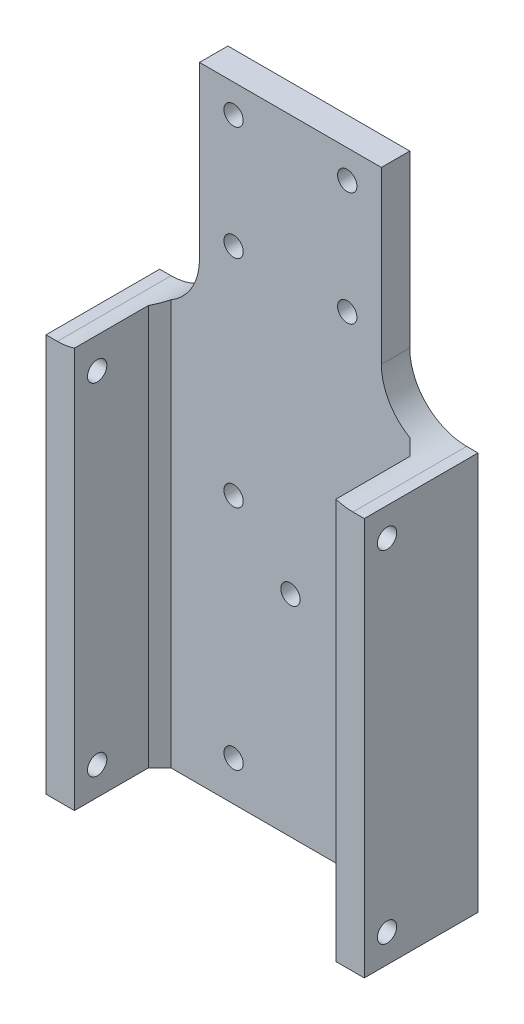
SolidWorks part; units mm, degrees
ref_plane "Front Plane" through (0, 0, 0) normal (0, 0, 1) x (1, 0, 0)
ref_plane "Top Plane" through (0, 0, 0) normal (0, 1, 0) x (1, 0, 0)
ref_plane "Right Plane" through (0, 0, 0) normal (1, 0, 0) x (0, 0, -1)
sketch "Sketch1" plane through (0, 0, 0) normal (0, 1, 0) x (1, 0, 0)
  line L1 (16, 2.5) -> (-16, 2.5)
  line L2 (16, 2.5) -> (16, -2.5)
  line L3 (16, -2.5) -> (-16, -2.5)
  line L4 (-16, 2.5) -> (-16, -2.5)
  line L5 (16, 2.5) -> (-16, -2.5) construction
  line L6 (16, -2.5) -> (-16, 2.5) construction
  point P0 (0, 0)
  dimension "D1" = 5
  dimension "D2" = 32
extrude "Boss-Extrude1" add sketch "Sketch1" along normal blind 40
hole_wizard "M3 Clearance Hole3" positions "Sketch2" profile "Sketch3" hole size "M3" standard "ANSI Metric" end condition through all
sketch "Sketch2" plane through (0, 0, 2.5) normal (0, 0, 1) x (1, 0, 0)
  line L1 (-10, 35) -> (10, 35) construction
  line L2 (10, 35) -> (10, 15) construction
  line L3 (10, 15) -> (-10, 15) construction
  line L4 (-10, 15) -> (-10, 35) construction
  line L5 (0, 0) -> (0, 15) construction
  line L7 (-16, 40) -> (16, 40) construction
  point P14 (-10, 35)
  point P15 (10, 35)
  point P17 (10, 15)
  point P19 (-10, 15)
  dimension "D1" = 20
  dimension "D2" = 5
sketch "Sketch3" plane through (-10, 35, 2.5) normal (1, 0, 0) x (0, -1, 0)
  line L0 (0, 0) -> (0, 5)
  line L1 (0, 5) -> (1.7, 5)
  line L2 (1.7, 5) -> (1.7, 0)
  line L5 (1.7, 0) -> (0, 0)
  line L11 (0, -6.35) -> (0, 107.95) construction
  dimension "Thru Hole Dia." = 3.4
  dimension "Thru Hole Depth" = 5
sketch "Sketch4" plane through (0, 0, 0) normal (0, 1, 0) x (1, 0, 0)
  line L0 (-16, -2.5) -> (16, -2.5) construction
  line L1 (-23, 2.5) -> (23, 2.5)
  line L2 (-23, 2.5) -> (-23, -2.5)
  line L3 (-23, -2.5) -> (23, -2.5)
  line L4 (23, 2.5) -> (23, -2.5)
  line L5 (0, -2.5) -> (0, 2.5) construction
  line L6 (-23, 0) -> (23, 0) construction
  line L7 (16, 2.5) -> (-16, 2.5) construction
  point P412 (0, 0)
  dimension "D2" = 46
extrude "Boss-Extrude2" add sketch "Sketch4" against normal blind 70
sketch "Sketch5" plane through (0, 0, 0) normal (0, 1, 0) x (1, 0, 0)
  line L0 (0, 0) -> (0, -2.5) construction
  line L1 (-16, -2.5) -> (16, -2.5) construction
  line L2 (-23, -7.5) -> (-28, -7.5) construction
  line L3 (23, 2.5) -> (28, 2.5)
  line L4 (23, 2.5) -> (23, -17.5)
  line L5 (23, -17.5) -> (28, -17.5)
  line L6 (28, 2.5) -> (28, -17.5)
  line L7 (25.5, -17.5) -> (25.5, 2.5) construction
  line L8 (23, -7.5) -> (28, -7.5) construction
  line L9 (-25.5, -17.5) -> (-25.5, 2.5) construction
  line L10 (-28, 2.5) -> (-28, -17.5)
  line L11 (-23, -17.5) -> (-28, -17.5)
  line L12 (-23, 2.5) -> (-23, -17.5)
  line L13 (-23, 2.5) -> (-28, 2.5)
  point P17 (-25.5, -7.5)
  point P261 (25.5, -7.5)
  dimension "D1" = 20
  dimension "D2" = 5
extrude "Boss-Extrude3" add sketch "Sketch5" against normal blind 70
hole_wizard "M3 Clearance Hole1" positions "Sketch6" profile "Sketch7" hole size "M3" standard "ANSI Metric" end condition through all
sketch "Sketch6" plane through (28, 0, 0) normal (1, 0, 0) x (0, 0, -1)
  line L0 (-17.5, -35) -> (2.5, -35) construction
  line L1 (-17.5, -70) -> (-17.5, 0) construction
  line L2 (2.5, -70) -> (2.5, 0) construction
  line L4 (-2.5, 40) -> (-2.5, 0) construction
  point P0 (-13.5, -5)
  point P2 (-13.5, -65)
  dimension "D1" = 60
  dimension "D2" = 11
sketch "Sketch7" plane through (28, -5, 13.5) normal (0, 1, 0) x (0, 0, -1)
  line L0 (0, 0) -> (0, 56)
  line L1 (0, 56) -> (1.7, 56)
  line L2 (1.7, 56) -> (1.7, 0)
  line L5 (1.7, 0) -> (0, 0)
  line L11 (0, -6.35) -> (0, 107.95) construction
  dimension "Thru Hole Dia." = 3.4
  dimension "Thru Hole Depth" = 56
hole_wizard "M3 Clearance Hole2" positions "Sketch8" profile "Sketch9" hole size "M3" standard "ANSI Metric" end condition through all
sketch "Sketch8" plane through (0, 0, -2.5) normal (0, 0, -1) x (-1, 0, 0)
  point P0 (-10, -23)
  point P2 (10, -23)
  point P5 (0, -33)
  point P8 (-10, -63)
  point P11 (10, -63)
sketch "Sketch9" plane through (10, -23, -2.5) normal (1, 0, 0) x (0, 1, 0)
  line L0 (0, 0) -> (0, 20)
  line L1 (0, 20) -> (1.7, 20)
  line L2 (1.7, 20) -> (1.7, 0)
  line L5 (1.7, 0) -> (0, 0)
  line L11 (0, -6.35) -> (0, 107.95) construction
  dimension "Thru Hole Dia." = 3.4
  dimension "Thru Hole Depth" = 20
sketch "Sketch10" plane through (28, 0, 0) normal (1, 0, 0) x (0, 0, -1)
  line L0 (-17.5, -70) -> (-17.5, 0) construction
  line L1 (-17.5, -60) -> (-4.5, -60)
  line L2 (-17.5, -60) -> (-17.5, -10)
  line L3 (-17.5, -10) -> (-4.5, -10)
  line L4 (-4.5, -60) -> (-4.5, -10)
  line L5 (-17.5, 0) -> (2.5, 0) construction
  line L6 (-17.5, -70) -> (2.5, -70) construction
  line L7 (2.5, -70) -> (2.5, 0) construction
  dimension "D1" = 10
  dimension "D2" = 10
  dimension "D3" = 7
extrude "Cut-Extrude1" [suppressed] cut sketch "Sketch10" against normal through all
fillet "Fillet2" radius 10 2 edges at (-16, 0, 0) (16, 0, 0)
fillet "Fillet3" [suppressed] radius 7 profile chamfer
fillet "Fillet4" radius 2 2 edges at (23, -34.7697, 2.5) (-23, -34.7697, 2.5) profile chamfer
fillet "Fillet5" [suppressed] type full round
fillet "Fillet6" [suppressed] type full round
fillet "Fillet7" [suppressed] type full round
fillet "Fillet8" [suppressed] type full round
fillet "Fillet9" [suppressed] radius 5
